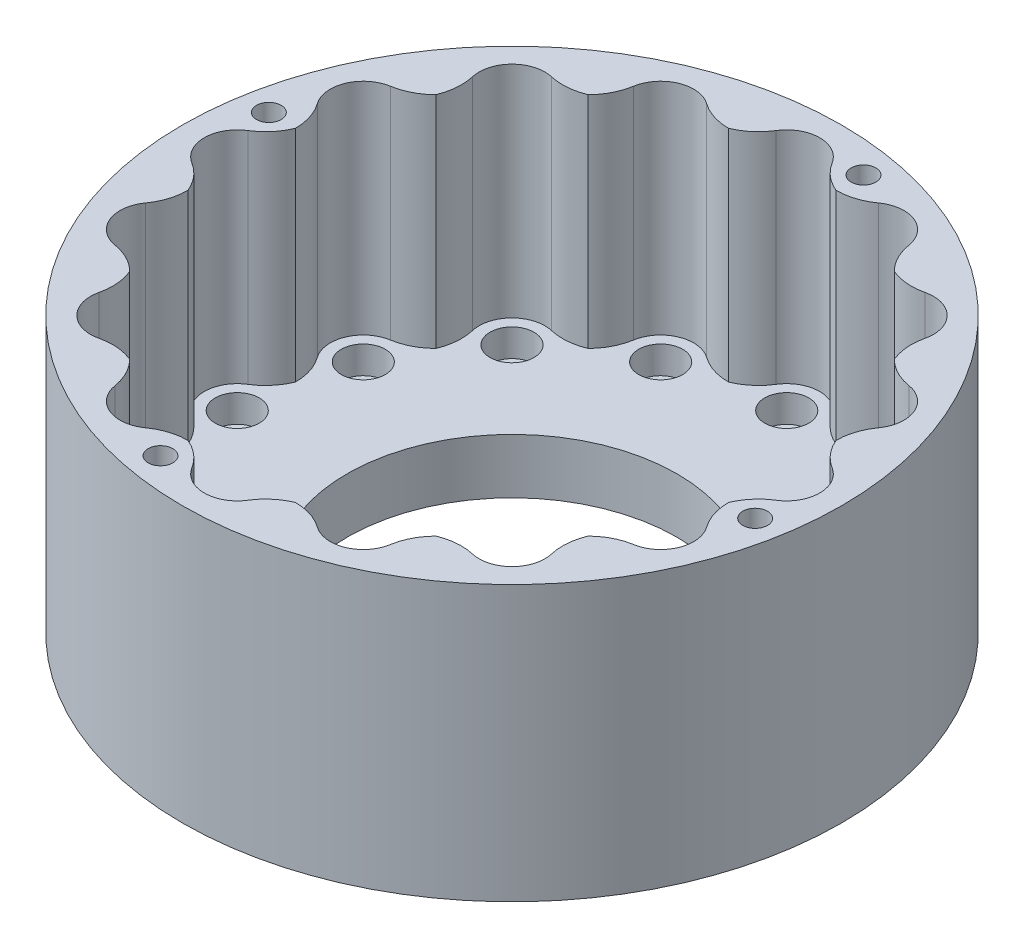
SolidWorks part; units mm, degrees
ref_plane "Front Plane" through (0, 0, 0) normal (0, 0, 1) x (1, 0, 0)
ref_plane "Top Plane" through (0, 0, 0) normal (0, 1, 0) x (1, 0, 0)
ref_plane "Right Plane" through (0, 0, 0) normal (1, 0, 0) x (0, 0, -1)
sketch "Sketch1" plane through (0, 0, 0) normal (0, 1, 0) x (1, 0, 0)
  arc A0 (-50.0283, 13.4631) -> (-51.515, 5.9892) centre (-1.875, 0) ccw
  arc A1 (4.1142, 49.64) -> (-7.8642, 49.64) centre (-1.875, 50) ccw
  arc A2 (-16.6515, 42.0695) -> (-16.6233, 42.0995) centre (-21.0092, 46.194) ccw
  arc A3 (-32.7408, 39.3358) -> (-41.2108, 30.8658) centre (-37.2303, 35.3553) ccw
  arc A4 (-45.4444, 24.5297) -> (-50.0283, 13.4631) centre (-48.069, 19.1342) ccw
  arc A5 (-51.515, 5.9892) -> (-51.515, -5.9892) centre (-51.875, 0) ccw
  arc A6 (-50.0283, -13.4631) -> (-45.4444, -24.5297) centre (-48.069, -19.1342) ccw
  arc A7 (-41.2108, -30.8658) -> (-32.7408, -39.3358) centre (-37.2303, -35.3553) ccw
  arc A8 (-26.4047, -43.5694) -> (-15.3381, -48.1533) centre (-21.0092, -46.194) ccw
  arc A9 (-7.8642, -49.64) -> (4.1142, -49.64) centre (-1.875, -50) ccw
  arc A10 (11.5881, -48.1533) -> (22.6547, -43.5694) centre (17.2592, -46.194) ccw
  arc A11 (28.9908, -39.3358) -> (37.4608, -30.8658) centre (33.4803, -35.3553) ccw
  arc A12 (40.4731, -14.5288) -> (40.4074, -14.5845) centre (44.319, -19.1342) ccw
  arc A13 (47.765, -5.9892) -> (47.765, 5.9892) centre (48.125, 0) ccw
  arc A14 (40.4074, 14.5845) -> (40.4731, 14.5288) centre (44.319, 19.1342) ccw
  arc A15 (37.4608, 30.8658) -> (28.9908, 39.3358) centre (33.4803, 35.3553) ccw
  arc A16 (22.6547, 43.5694) -> (11.5881, 48.1533) centre (17.2592, 46.194) ccw
  circle A17 centre (-1.875, 0) radius 60
  arc A18 (-41.2108, 30.8658) -> (-45.4444, 24.5297) centre (-1.875, 0) ccw
  arc A19 (-26.4047, 43.5694) -> (-32.7408, 39.3358) centre (-1.875, 0) ccw
  arc A20 (-15.3381, 48.1533) -> (-26.4047, 43.5694) centre (-21.0092, 46.194) ccw
  arc A21 (-7.8642, 49.64) -> (-15.3381, 48.1533) centre (-1.875, 0) ccw
  arc A22 (11.5881, 48.1533) -> (4.1142, 49.64) centre (-1.875, 0) ccw
  arc A23 (28.9908, 39.3358) -> (22.6547, 43.5694) centre (-1.875, 0) ccw
  arc A24 (41.6944, 24.5297) -> (37.4608, 30.8658) centre (-1.875, 0) ccw
  arc A25 (46.2783, 13.4631) -> (41.6944, 24.5297) centre (44.319, 19.1342) ccw
  arc A26 (46.2783, -13.4631) -> (47.765, -5.9892) centre (-1.875, 0) ccw
  arc A27 (41.6944, -24.5297) -> (46.2783, -13.4631) centre (44.319, -19.1342) ccw
  arc A28 (37.4608, -30.8658) -> (41.6944, -24.5297) centre (-1.875, 0) ccw
  arc A29 (-51.515, -5.9892) -> (-50.0283, -13.4631) centre (-1.875, 0) ccw
  arc A30 (-45.4444, -24.5297) -> (-41.2108, -30.8658) centre (-1.875, 0) ccw
  arc A31 (-32.7408, -39.3358) -> (-26.4047, -43.5694) centre (-1.875, 0) ccw
  arc A32 (-15.3381, -48.1533) -> (-7.8642, -49.64) centre (-1.875, 0) ccw
  arc A33 (-16.6233, -42.0995) -> (-16.6515, -42.0695) centre (-21.0092, -46.194) ccw
  arc A34 (4.1142, -49.64) -> (11.5881, -48.1533) centre (-1.875, 0) ccw
  arc A35 (22.6547, -43.5694) -> (28.9908, -39.3358) centre (-1.875, 0) ccw
  arc A36 (47.765, 5.9892) -> (46.2783, 13.4631) centre (-1.875, 0) ccw
  spline S0 degree 4 poles (44.0747, 11.4987) (44.2543, 11.2167) (44.5698, 10.6242) (44.9021, 9.6808) (45.0642, 8.3642) (44.9446, 7.1282) (44.593, 6.0249) (44.1211, 5.1947) (43.695, 4.5754) (43.3564, 4.0472) (43.0998, 3.6163) (42.8821, 3.198) (42.6994, 2.7973) (42.5503, 2.4153) (42.4301, 2.0557) (42.3415, 1.7357) (42.2778, 1.4587) (42.224, 1.1791) (42.1875, 0.9457) (42.1595, 0.7089) (42.1421, 0.4978) (42.1336, 0.3578) (42.1278, 0.2085) (42.1243, 0.037) (42.1247, -0.0678) (42.1293, -0.2634) (42.1379, -0.4367) (42.15, -0.5999) (42.1691, -0.7936) (42.1974, -1.0101) (42.2414, -1.2799) (42.3074, -1.6012) (42.4037, -1.9716) (42.5387, -2.3877) (42.6983, -2.7948) (42.8796, -3.1931) (43.1366, -3.6835) (43.482, -4.2594) (43.9287, -4.9065) (44.4091, -5.6745) (44.8007, -6.6105) (45.0295, -7.7093) (45.0295, -8.9484) (44.7352, -10.2696) (44.1902, -11.4212) (43.4619, -12.3657) (42.6206, -13.0778) (41.7593, -13.602) (40.7824, -14.2408) (39.77, -15.1062) (38.838, -16.2841) (38.1405, -17.7977) (37.8498, -19.2831) (37.8586, -20.6377) (38.0279, -21.8199) (38.2279, -22.8394) (38.2788, -23.9779) (38.0615, -25.1966) (37.5489, -26.4121) (36.7247, -27.5436) (35.7476, -28.3911) (34.706, -28.96) (33.6586, -29.2738) (32.6702, -29.405) (31.5286, -29.5836) (30.2595, -29.9481) (28.9262, -30.6268) (27.659, -31.7106) (26.7717, -32.9447) (26.2118, -34.1914) (25.9145, -35.2243) (25.7304, -35.9895) (25.5039, -36.7438) (25.1586, -37.555) (24.5413, -38.4785) (23.5696, -39.3957) (22.3328, -40.1097) (21.0527, -40.4927) (19.9443, -40.5655) (19.0691, -40.4589) (18.3026, -40.2779) (17.5479, -40.0547) (16.5047, -39.7958) (15.1451, -39.6573) (13.6327, -39.8087) (12.0605, -40.3642) (10.8061, -41.1795) (9.8558, -42.0964) (9.1304, -42.9957) (8.5226, -43.7861) (7.7271, -44.5363) (6.7136, -45.1539) (5.4911, -45.5763) (4.0991, -45.7244) (2.7902, -45.5605) (1.6261, -45.1394) (0.6656, -44.526) (-0.1173, -43.8431) (-1.0565, -43.1053) (-2.2252, -42.4205) (-3.657, -41.9295) (-5.3166, -41.7767) (-6.8026, -41.9949) (-8.0583, -42.439) (-9.1, -42.9656) (-9.9846, -43.4494) (-11.0219, -43.8219) (-12.2041, -43.9805) (-13.4901, -43.8751) (-14.8122, -43.455) (-15.9301, -42.7928) (-16.8127, -41.9651) (-17.4446, -41.0507) (-17.8788, -40.1387) (-18.4163, -39.084) (-19.1877, -37.9587) (-20.2985, -36.882) (-21.7915, -36.02) (-23.2794, -35.5964) (-24.6396, -35.491) (-25.8217, -35.5529) (-26.8286, -35.6328) (-27.9365, -35.5428) (-29.0946, -35.1922) (-30.227, -34.5552) (-31.2519, -33.6204) (-31.9862, -32.5593) (-32.4399, -31.4562) (-32.636, -30.3717) (-32.6594, -29.3636) (-32.7241, -28.1982) (-32.9674, -26.8887) (-33.5214, -25.4926) (-34.4835, -24.1318) (-35.6246, -23.1374) (-36.8021, -22.4676) (-37.9106, -22.0232) (-38.8934, -21.6866) (-39.9049, -21.1614) (-40.8517, -20.3639) (-41.648, -19.3123) (-42.2158, -18.0327) (-42.4612, -16.7628) (-42.4331, -15.5762) (-42.1811, -14.5123) (-41.8006, -13.5907) (-41.3845, -12.5128) (-41.0655, -11.2314) (-40.9867, -9.7374) (-41.2916, -8.0981) (-41.8623, -6.8333) (-42.485, -5.9251) (-43.0125, -5.3085) (-43.3736, -4.9275) (-43.7476, -4.5595) (-44.1231, -4.193) (-44.4829, -3.8105) (-44.8105, -3.3997) (-45.0744, -2.9955) (-45.2825, -2.6081) (-45.444, -2.2456) (-45.5676, -1.9138) (-45.6577, -1.6174) (-45.7221, -1.3598) (-45.7672, -1.1433) (-45.7981, -0.9691) (-45.8239, -0.7941) (-45.8419, -0.6396) (-45.8542, -0.5087) (-45.8622, -0.3996) (-45.8674, -0.31) (-45.8722, -0.1929) (-45.8754, -0.0484) (-45.8754, 0.057) (-45.8707, 0.2539) (-45.8614, 0.4217) (-45.8475, 0.5867) (-45.8289, 0.7543) (-45.8057, 0.9209) (-45.7778, 1.0866) (-45.7208, 1.3751) (-45.6162, 1.7824) (-45.4517, 2.2512) (-45.2056, 2.7679) (-44.9364, 3.2145) (-44.6596, 3.5954) (-44.3529, 3.9526) (-44.0247, 4.2897) (-43.6878, 4.6178) (-43.3537, 4.9489) (-43.036, 5.2844) (-42.7388, 5.6275) (-42.4647, 5.9787) (-42.2147, 6.3375) (-41.9285, 6.8032) (-41.6301, 7.388) (-41.2988, 8.2445) (-41.0869, 9.2182) (-41.0245, 10.1783) (-41.079, 10.9169) (-41.1306, 11.2832) (-41.1623, 11.4653) knots 0 0 0 0 0 0.00752 0.015039 0.022311 0.029582 0.03522 0.040858 0.043677 0.046496 0.049315 0.052134 0.054265 0.056396 0.058526 0.060657 0.061722 0.062788 0.064918 0.065984 0.067049 0.067582 0.068115 0.06918 0.070492 0.071149 0.071805 0.073033 0.074262 0.07549 0.076719 0.079176 0.081633 0.084089 0.086546 0.089003 0.09146 0.096539 0.101618 0.106697 0.111776 0.11923 0.126684 0.134323 0.141963 0.147625 0.153288 0.15895 0.164612 0.173852 0.183092 0.192408 0.201724 0.207559 0.213395 0.219231 0.225067 0.233024 0.240981 0.24862 0.25626 0.261858 0.267455 0.273053 0.278651 0.287828 0.297005 0.30639 0.315776 0.321674 0.327572 0.330521 0.33347 0.339368 0.347323 0.355277 0.363232 0.371186 0.377084 0.380033 0.382982 0.38888 0.394778 0.404164 0.413549 0.422726 0.431904 0.437501 0.443099 0.448697 0.454294 0.461934 0.469574 0.477531 0.485487 0.491323 0.497159 0.502995 0.508831 0.518146 0.527462 0.536702 0.545942 0.551604 0.557267 0.562929 0.568591 0.576231 0.58387 0.591691 0.599511 0.605182 0.610853 0.616525 0.622196 0.631785 0.641374 0.650964 0.660553 0.666224 0.671895 0.677566 0.683238 0.691058 0.698878 0.706518 0.714157 0.71982 0.725482 0.731145 0.736807 0.746047 0.755287 0.764602 0.773918 0.779754 0.78559 0.791426 0.797261 0.805218 0.813175 0.820815 0.828454 0.834052 0.83965 0.845248 0.850845 0.860022 0.869199 0.878585 0.887971 0.89092 0.893869 0.896818 0.899767 0.902716 0.905665 0.908614 0.911563 0.913551 0.91554 0.917528 0.919517 0.920511 0.921506 0.9225 0.923494 0.924489 0.924986 0.925483 0.92598 0.926477 0.927472 0.928416 0.929361 0.930305 0.931249 0.932194 0.933138 0.934083 0.935027 0.938805 0.942583 0.945226 0.947869 0.950513 0.953156 0.955799 0.958442 0.961086 0.963729 0.966185 0.968641 0.971097 0.973554 0.978466 0.983378 0.991689 0.995845 1 1 1 1 1 construction
  spline S1 degree 4 poles (40.4731, -14.5288) (40.4566, -14.5426) (40.4402, -14.5565) (40.4237, -14.5705) (40.4074, -14.5845) knots 0.165033 0.165033 0.165033 0.165033 0.165033 0.165518 0.165518 0.165518 0.165518 0.165518
  spline S2 degree 4 poles (40.4731, 14.5288) (40.4566, 14.5426) (40.4402, 14.5565) (40.4237, 14.5705) (40.4074, 14.5845) knots 0.165033 0.165033 0.165033 0.165033 0.165033 0.165518 0.165518 0.165518 0.165518 0.165518
  spline S3 degree 4 poles (-16.6233, 42.0995) (-16.6304, 42.0921) (-16.6375, 42.0846) (-16.6445, 42.0771) (-16.6515, 42.0695) knots 0.600544 0.600544 0.600544 0.600544 0.600544 0.600775 0.600775 0.600775 0.600775 0.600775
  dimension "D1" = 16
extrude "Boss-Extrude1" add sketch "Sketch1" along normal blind 50 contours A17 | A26 A13 A36 A25 A24 A15 A23 A16 A22 A1 A21 A20 A19 A3 A18 A4 A0 A5 A29 A6 A30 A7 A31 A8 A32 A9 A34 A10 A35 A11 A28 A27
sketch "Sketch3" plane through (0, 0, 0) normal (0, 1, 0) x (1, 0, 0)
  circle A0 centre (-1.875, 0) radius 60
extrude "Boss-Extrude2" add sketch "Sketch3" along normal blind 10
fillet "Fillet1" radius 10 2 edges at (11.5881, 30, -48.1533) (4.1142, 30, -49.64)
fillet "Fillet2" radius 10 30 edges at (-50.0283, 30, -13.4631) (-51.515, 30, -5.9892) (-51.515, 30, 5.9892) (-50.0283, 30, 13.4631) (-45.4444, 30, 24.5297) (-41.2108, 30, 30.8658) (-32.7408, 30, 39.3358) (-26.4047, 30, 43.5694) (-15.3381, 30, 48.1533) (-7.8642, 30, 49.64) (-45.4444, 30, -24.5297) (-41.2108, 30, -30.8658) (-32.7408, 30, -39.3358) (-26.4047, 30, -43.5694) (-7.8642, 30, -49.64) (-15.3381, 30, -48.1533) (4.1142, 30, 49.64) (11.5881, 30, 48.1533) (22.6547, 30, 43.5694) (28.9908, 30, 39.3358) (37.4608, 30, 30.8658) (41.6944, 30, 24.5297) (46.2783, 30, 13.4631) (47.765, 30, 5.9892) (47.765, 30, -5.9892) (46.2783, 30, -13.4631) (41.6944, 30, -24.5297) (37.4608, 30, -30.8658) (28.9908, 30, -39.3358) (22.6547, 30, -43.5694)
sketch "Sketch5" plane through (0, 50, 0) normal (0, 1, 0) x (1, 0, 0)
  circle A0 centre (-11.7359, -54.1088) radius 2.25
  circle A3 centre (-55.9838, 9.8609) radius 2.25
  circle A4 centre (7.9859, 54.1088) radius 2.25
  circle A5 centre (52.2338, -9.8609) radius 2.25
  point P12 (-1.875, 0)
  dimension "D1" = 4
extrude "Cut-Extrude2" cut sketch "Sketch5" against normal blind 6.1 contours A4 | A3 | A0 | A5 region at (7.9859, 50, -54.1088)
sketch "Sketch6" plane through (0, 10, 0) normal (0, 1, 0) x (1, 0, 0)
  circle A0 centre (-1.875, 0) radius 50 construction
  circle A1 centre (-1.875, 50) radius 4
  circle A2 centre (17.2592, 46.194) radius 4
  circle A3 centre (33.4803, 35.3553) radius 4
  circle A4 centre (44.319, 19.1342) radius 4
  circle A5 centre (48.125, 0) radius 4
  circle A6 centre (44.319, -19.1342) radius 4
  circle A7 centre (33.4803, -35.3553) radius 4
  circle A8 centre (17.2592, -46.194) radius 4
  circle A9 centre (-1.875, -50) radius 4
  circle A10 centre (-21.0092, -46.194) radius 4
  circle A11 centre (-37.2303, -35.3553) radius 4
  circle A12 centre (-48.069, -19.1342) radius 4
  circle A13 centre (-51.875, 0) radius 4
  circle A14 centre (-48.069, 19.1342) radius 4
  circle A15 centre (-37.2303, 35.3553) radius 4
  circle A16 centre (-21.0092, 46.194) radius 4
  dimension "D1" = 16
extrude "Cut-Extrude3" cut sketch "Sketch6" against normal blind 5
sketch "Sketch7" plane through (0, 0, 0) normal (0, -1, 0) x (1, 0, 0)
  circle A1 centre (-1.875, 0) radius 30.05
  point P0 (-1.875, 0)
  dimension "D1" = 60.1
extrude "Cut-Extrude4" cut sketch "Sketch7" against normal blind 10
